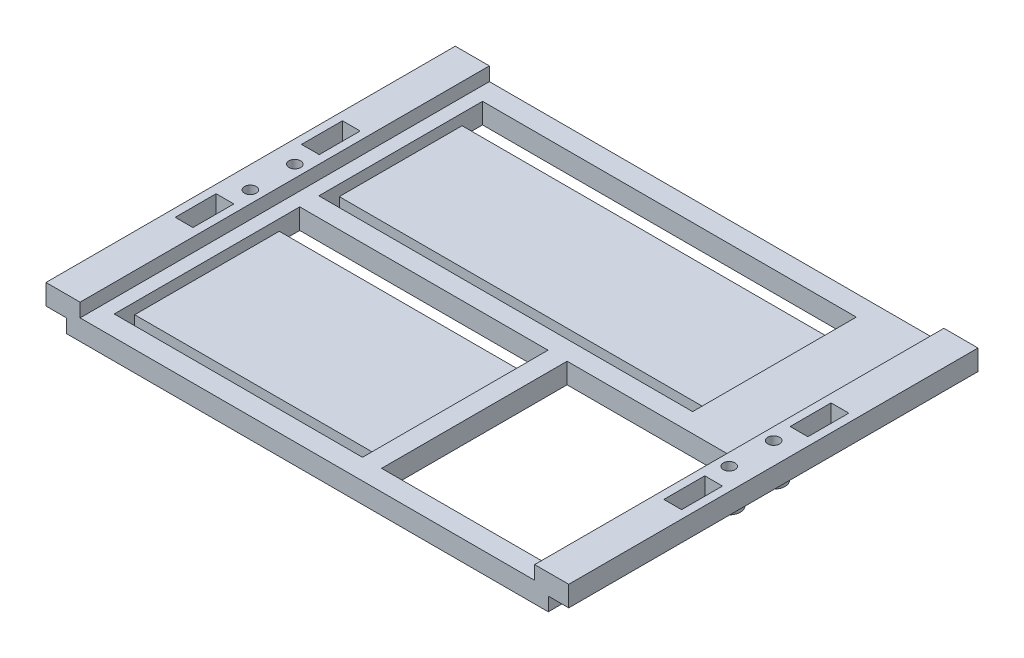
SolidWorks part; units mm, degrees
ref_plane "Front Plane" through (0, 0, 0) normal (0, 0, 1) x (1, 0, 0)
ref_plane "Top Plane" through (0, 0, 0) normal (0, 1, 0) x (1, 0, 0)
ref_plane "Right Plane" through (0, 0, 0) normal (1, 0, 0) x (0, 0, -1)
sketch "Sketch2" plane through (0, 0, 0) normal (0, 0, 1) x (1, 0, 0)
  line L0 (179.1, 12.5) -> (191.6, 12.5)
  line L1 (7.5, 0) -> (184.1, 0)
  line L2 (0, 5) -> (0, 12.5)
  line L3 (0, 12.5) -> (12.5, 12.5)
  line L4 (191.6, 5) -> (191.6, 12.5)
  line L7 (0, 5) -> (7.5, 5)
  line L8 (7.5, 0) -> (7.5, 5)
  line L11 (191.6, 5) -> (184.1, 5)
  line L12 (184.1, 0) -> (184.1, 5)
  line L14 (12.5, 12.5) -> (12.5, 7.5)
  line L15 (12.5, 7.5) -> (179.1, 7.5)
  line L16 (179.1, 12.5) -> (179.1, 7.5)
  dimension "D1" = 191.6
  dimension "D2" = 5
  dimension "D3" = 5
  dimension "D4" = 5
  dimension "D5" = 12.5
  dimension "D6" = 7.5
  dimension "D7" = 7.5
  dimension "D8" = 12.5
  dimension "D9" = 12.5
extrude "PlateFrame" add sketch "Sketch2" along normal blind 150
sketch "Sketch3" plane through (0, 12.5, 0) normal (0, 1, 0) x (1, 0, 0)
  line L0 (12.5, 0) -> (0, 0) construction
  line L2 (0, -150) -> (0, 0) construction
  line L3 (191.6, -150) -> (191.6, 0) construction
  line L4 (191.6, 0) -> (179.1, 0) construction
  circle A0 centre (8.05, -66.85) radius 2.5
  circle A1 centre (8.05, -83.15) radius 2.5
  circle A2 centre (183.55, -66.85) radius 2.5
  circle A3 centre (183.55, -83.15) radius 2.5
  dimension "D1" = 5
  dimension "D2" = 5
  dimension "D3" = 5
  dimension "D4" = 5
  dimension "D5" = 66.85
  dimension "D6" = 16.3
  dimension "D7" = 8.05
  dimension "D8" = 8.05
  dimension "D9" = 8.05
  dimension "D10" = 8.05
  dimension "D11" = 66.85
  dimension "D12" = 16.3
  dimension "D13" = 175.5
extrude "HoleSupport" cut sketch "Sketch3" against normal through all
sketch "Sketch4" plane through (0, 12.5, 0) normal (0, 1, 0) x (1, 0, 0)
  circle A0 centre (8.05, -66.85) radius 2.15
  circle A1 centre (8.05, -83.15) radius 2.15
  circle A2 centre (183.55, -83.15) radius 2.15
  circle A3 centre (183.55, -66.85) radius 2.15
  circle A4 centre (183.55, -66.85) radius 4.15
  circle A5 centre (183.55, -83.15) radius 4.15
  circle A6 centre (8.05, -66.85) radius 4.15
  circle A7 centre (8.05, -83.15) radius 4.15
  dimension "D1" = 2
extrude "CylindricalSupports" add sketch "Sketch4" against normal blind 12.5
sketch "Sketch8" plane through (0, 7.5, 0) normal (0, 1, 0) x (1, 0, 0)
  line L0 (12.5, -150) -> (12.5, 0) construction
  line L2 (154.5, -7.5) -> (17.5, -7.5)
  line L3 (154.5, -7.5) -> (154.5, -67.5)
  line L4 (154.5, -67.5) -> (17.5, -67.5)
  line L5 (17.5, -7.5) -> (17.5, -67.5)
  line L6 (108.5, -142.5) -> (17.5, -142.5)
  line L7 (108.5, -142.5) -> (108.5, -74.5)
  line L8 (108.5, -74.5) -> (17.5, -74.5)
  line L9 (17.5, -142.5) -> (17.5, -74.5)
  line L10 (179.1, 0) -> (12.5, 0) construction
  line L11 (179.1, -150) -> (12.5, -150) construction
  dimension "D1" = 5
  dimension "D2" = 7.5
  dimension "D3" = 7.5
  dimension "D4" = 5
  dimension "D5" = 60
  dimension "D6" = 68
  dimension "D7" = 137
  dimension "D8" = 91
extrude "ItemLayout" cut sketch "Sketch8" against normal blind 4
sketch "Sketch9" plane through (0, 7.5, 0) normal (0, 1, 0) x (1, 0, 0)
  line L0 (179.1, -150) -> (179.1, 0) construction
  line L1 (115.5, -74.5) -> (174.1, -74.5)
  line L2 (115.5, -74.5) -> (115.5, -142.5)
  line L3 (115.5, -142.5) -> (174.1, -142.5)
  line L4 (174.1, -74.5) -> (174.1, -142.5)
  line L5 (179.1, -150) -> (12.5, -150) construction
  line L7 (108.5, -142.5) -> (108.5, -74.5) construction
  dimension "D1" = 5
  dimension "D2" = 7.5
  dimension "D3" = 68
  dimension "D4" = 7
extrude "HoleCutout" cut sketch "Sketch9" against normal blind 7.5
sketch "Sketch10" plane through (0, 3.5, 0) normal (0, 1, 0) x (1, 0, 0)
  line L0 (108.5, -142.5) -> (108.5, -74.5) construction
  line L1 (17.5, -74.5) -> (108.5, -74.5)
  line L2 (17.5, -74.5) -> (17.5, -82)
  line L3 (17.5, -82) -> (108.5, -82)
  line L4 (108.5, -74.5) -> (108.5, -82)
  line L5 (108.5, -142.5) -> (108.5, -74.5) construction
  line L6 (17.5, -142.5) -> (108.5, -142.5)
  line L7 (17.5, -142.5) -> (17.5, -135)
  line L8 (17.5, -135) -> (108.5, -135)
  line L9 (108.5, -142.5) -> (108.5, -135)
  line L10 (154.5, -67.5) -> (154.5, -7.5) construction
  line L11 (17.5, -7.5) -> (154.5, -7.5)
  line L12 (17.5, -7.5) -> (17.5, -15)
  line L13 (17.5, -15) -> (154.5, -15)
  line L14 (154.5, -7.5) -> (154.5, -15)
  line L16 (17.5, -67.5) -> (154.5, -67.5)
  line L17 (17.5, -67.5) -> (17.5, -60)
  line L18 (17.5, -60) -> (154.5, -60)
  line L19 (154.5, -67.5) -> (154.5, -60)
  dimension "D1" = 7.5
  dimension "D2" = 7.5
  dimension "D3" = 7.5
  dimension "D4" = 7.5
extrude "VelcroCut" cut sketch "Sketch10" against normal blind 3.5
sketch "Sketch11" plane through (0, 12.5, 0) normal (0, 1, 0) x (1, 0, 0)
  line L0 (12.5, -150) -> (12.5, 0) construction
  line L1 (9.5, -59.35) -> (3, -59.35)
  line L2 (9.5, -59.35) -> (9.5, -44.35)
  line L3 (9.5, -44.35) -> (3, -44.35)
  line L4 (3, -59.35) -> (3, -44.35)
  line L5 (188.6, -59.35) -> (182.1, -59.35)
  line L6 (188.6, -59.35) -> (188.6, -44.35)
  line L7 (188.6, -44.35) -> (182.1, -44.35)
  line L8 (182.1, -59.35) -> (182.1, -44.35)
  line L9 (182.1, -90.65) -> (188.6, -90.65)
  line L10 (182.1, -90.65) -> (182.1, -105.65)
  line L11 (182.1, -105.65) -> (188.6, -105.65)
  line L12 (188.6, -90.65) -> (188.6, -105.65)
  line L13 (3, -90.65) -> (9.5, -90.65)
  line L14 (3, -90.65) -> (3, -105.65)
  line L15 (3, -105.65) -> (9.5, -105.65)
  line L16 (9.5, -90.65) -> (9.5, -105.65)
  line L17 (12.5, -150) -> (12.5, 0) construction
  line L18 (179.1, -150) -> (179.1, 0) construction
  line L19 (179.1, -150) -> (179.1, 0) construction
  circle A4 centre (8.05, -66.85) radius 2.15 construction
  circle A5 centre (8.05, -83.15) radius 2.15 construction
  circle A6 centre (183.55, -66.85) radius 2.15 construction
  circle A7 centre (183.55, -83.15) radius 2.15 construction
  dimension "D2" = 7.5
  dimension "D12" = 7.5
  dimension "D11" = 7.5
  dimension "D17" = 7.5
  dimension "D3" = 3
  dimension "D4" = 3
  dimension "D5" = 6.5
  dimension "D6" = 15
  dimension "D7" = 6.5
  dimension "D8" = 15
  dimension "D9" = 3
  dimension "D10" = 3
  dimension "D13" = 15
  dimension "D14" = 15
  dimension "D15" = 6.5
  dimension "D16" = 6.5
extrude "CutShellHoles" cut sketch "Sketch11" against normal blind 12.5
